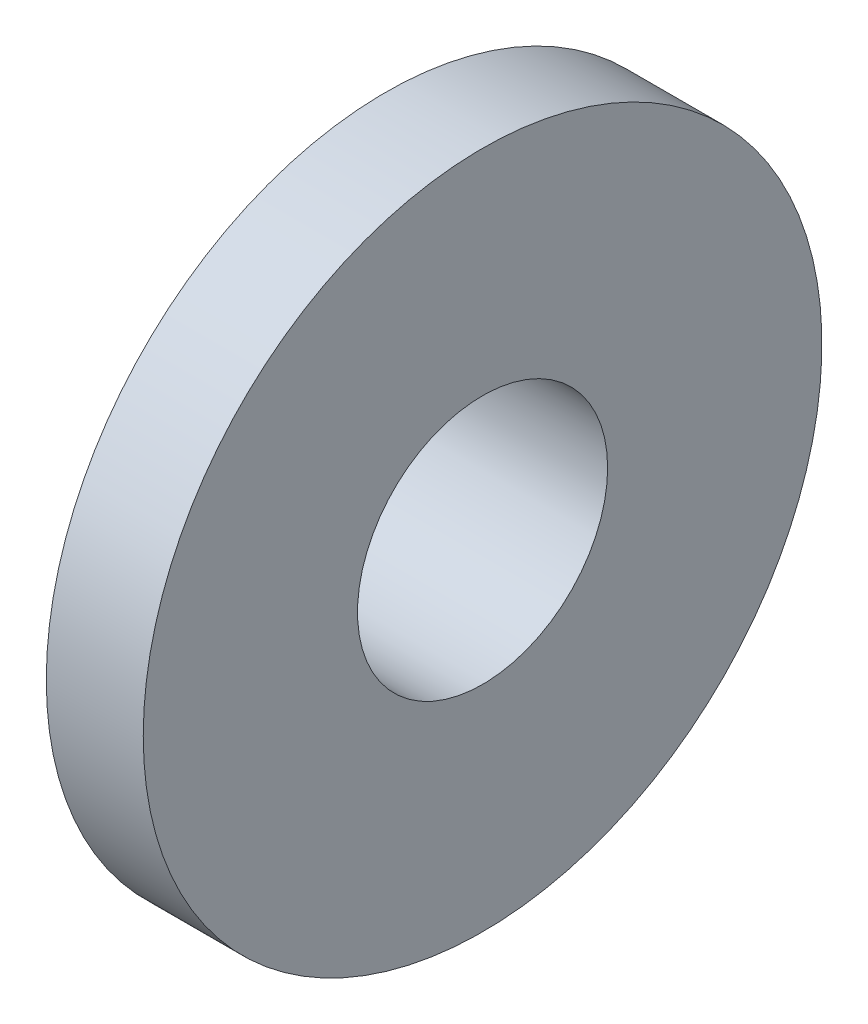
SolidWorks part; units mm, degrees
material "PLA2"
ref_plane "Front Plane" through (0, 0, 0) normal (0, 0, 1) x (1, 0, 0)
ref_plane "Top Plane" through (0, 0, 0) normal (0, 1, 0) x (1, 0, 0)
ref_plane "Right Plane" through (0, 0, 0) normal (1, 0, 0) x (0, 0, -1)
sketch "Sketch1" plane through (0, 0, 0) normal (1, 0, 0) x (0, 0, -1)
  circle A0 centre (0, 0) radius 3.2766
  circle A1 centre (0, 0) radius 4.826
  dimension "D1" = 6.5532
  dimension "D2" = 9.652
extrude "Boss-Extrude1" add sketch "Sketch1" along normal blind 5.334
sketch "Sketch2" plane through (5.334, 0, 0) normal (-1, 0, 0) x (0, 0, 1)
  circle A0 centre (0, 0) radius 8.89
  circle A1 centre (0, 0) radius 3.2766 construction
  circle A2 centre (0, 0) radius 3.2766
  dimension "D1" = 17.78
extrude "Boss-Extrude2" add sketch "Sketch2" along normal blind 2.54
fillet "Fillet1" radius 0.889 1 edges at (2.794, 0, 4.826)
